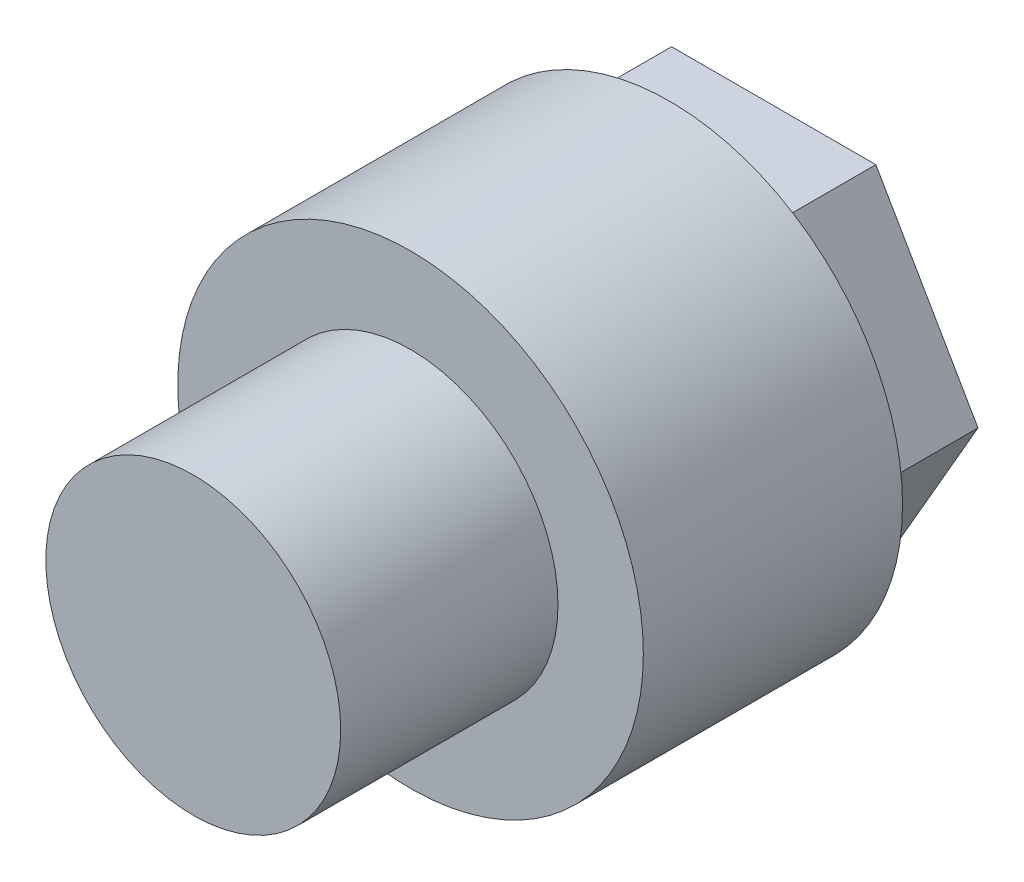
SolidWorks part; units mm, degrees
note: The reader was unsure of these and kept them because the rebuilt part matched: shared geometry of "Sketch1<3>", "Sketch1<4>".
ref_plane "Front Plane" through (0, 0, 0) normal (0, 0, 1) x (1, 0, 0)
ref_plane "Top Plane" through (0, 0, 0) normal (0, 1, 0) x (1, 0, 0)
ref_plane "Right Plane" through (0, 0, 0) normal (1, 0, 0) x (0, 0, -1)
sketch "Sketch1" plane through (0, 0, 0) normal (0, 0, 1) x (1, 0, 0)
  line L0 (-3.2909, -5.7) -> (3.2909, -5.7)
  line L1 (3.2909, -5.7) -> (6.5818, 0)
  line L2 (6.5818, 0) -> (3.2909, 5.7)
  line L3 (3.2909, 5.7) -> (-3.2909, 5.7)
  line L4 (-3.2909, 5.7) -> (-6.5818, 0)
  line L5 (-6.5818, 0) -> (-3.2909, -5.7)
  circle A0 centre (0, 0) radius 4.75
  circle A1 centre (0, 0) radius 7.5
  point P8 (0, 0)
  point P10 (0, 5.7)
  dimension "D3" = 15
  dimension "D4" = 9.5
  dimension "D1" = 120
  dimension "D2" = 11.4
extrude "Boss-Extrude1" add sketch "Sketch1" along normal blind 8.35 contours L4 L5 L0 L1 L2 L3 A1 | A0 | A1 A0
extrude "Boss-Extrude2" add sketch "Sketch1<3>" against normal blind 3.35 contours A1 A0 | A0
sketch "Sketch1<3>" plane through (0, 0, 0) normal (0, 0, 1) x (1, 0, 0) same geometry as "Sketch1"
ref_plane "Plane1" through (0, 0, 4.175) normal (0, 0, 1) x (1, 0, 0)
extrude "Boss-Extrude3" add sketch "Sketch1<4>" along normal blind 7 from surface at 8.35 contours A0 starting at face at (7.5, 0, 8.35)
sketch "Sketch1<4>" plane through (0, 0, 0) normal (0, 0, 1) x (1, 0, 0) same geometry as "Sketch1"
